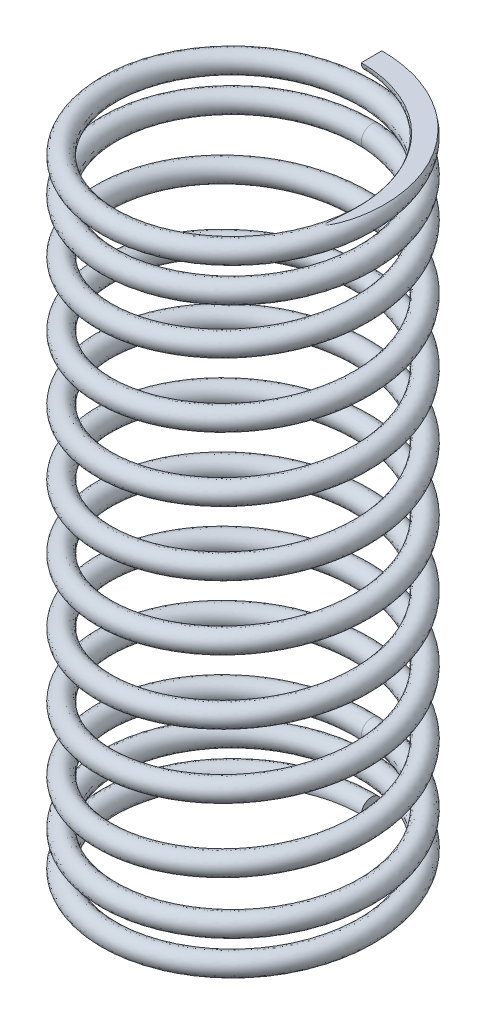
SolidWorks part; units mm, degrees
note: '?' marks a value the reader was unsure of.
ref_plane "Front" through (0, 0, 0) normal (0, 0, 1) x (1, 0, 0)
ref_plane "Top" through (0, 0, 0) normal (0, 1, 0) x (1, 0, 0)
ref_plane "Right" through (0, 0, 0) normal (1, 0, 0) x (0, 0, -1)
sketch "Sketch1" plane through (0, 0, 0) normal (0, 1, 0) x (1, 0, 0)
  circle A0 centre (0, 0) radius 4.7625
  dimension "D1" = 9.525
curve "Helix/Spiral1" pitch 2.3813 height 19.05 turns 8
sketch "Sketch2" plane through (0, 0, 0) normal (1, 0, 0) x (0, 0, -1)
  circle A0 centre (4.7625, 0) radius 0.381
  dimension "D1" = 0.762
sweep "Sweep1" add profiles "Sketch2" path "Helix/Spiral1"
sketch "Sketch3" plane through (0, 0, 0) normal (0, 1, 0) x (1, 0, 0)
  circle A0 centre (0, 0) radius 4.7625 construction
  circle A1 centre (0, 0) radius 4.7625
curve "Helix/Spiral2" pitch 1.27 height 2.54 turns 2
sketch "Sketch4" plane through (0, 0, 0) normal (1, 0, 0) x (0, 0, -1)
  circle A1 centre (4.7625, 0) radius 0.381
  circle A2 centre (4.7625, 0) radius 0.381
  dimension "D1" = 0
sweep "Sweep2" add profiles "Sketch4" path "Helix/Spiral2"
sketch "Sketch5" plane through (0, 0, 0) normal (-1, 0, 0) x (0, 0, 1)
  point P0 (-4.7625, 19.05)
ref_plane "Plane1" through (0, 19.05, 0) normal (0, 1, 0) x (1, 0, 0)
sketch "Sketch6" plane through (0, 19.05, 0) normal (0, 1, 0) x (1, 0, 0)
  circle A1 centre (0, 0) radius 4.7625
  circle A2 centre (0, 0) radius 4.7625
  dimension "D1" = 0
curve "Helix/Spiral3" pitch 1.27 height 2.54 turns 2
sketch "Sketch7" plane through (0, 0, 0) normal (-1, 0, 0) x (0, 0, 1)
  circle A1 centre (-4.7625, 19.05) radius 0.381
  circle A2 centre (-4.7625, 19.05) radius 0.381
  dimension "D1" = 0
sweep "Sweep3" add profiles "Sketch7" path "Helix/Spiral3"
sketch "Sketch8" plane through (0, 0, 0) normal (1, 0, 0) x (0, 0, -1)
  line L0 (6.35, 21.59) -> (-6.35, 21.59)
  dimension "D1" = 21.59
  dimension "D2" = 12.7
  dimension "D3" = 6.35
extrude "Cut-Extrude1" cut sketch "Sketch8" against normal through all both and the other way through all flip side to cut
sketch "Sketch10" plane through (0, 0, 0) normal (1, 0, 0) x (0, 0, -1)
  line L0 (6.35, -2.54) -> (-6.35, -2.54)
  dimension "D2" = 12.7
  dimension "D3" = 6.35
extrude "Cut-Extrude2" cut sketch "Sketch10" against normal through all both and the other way through all
ref_axis "Axis1" through (0, 50, 0) along (0, -1, 0)?
equation "\"D3@Sketch8\"=\"D2@Sketch8\"/2"
equation "\"D3@Sketch10\"=\"D2@Sketch10\"/2"
